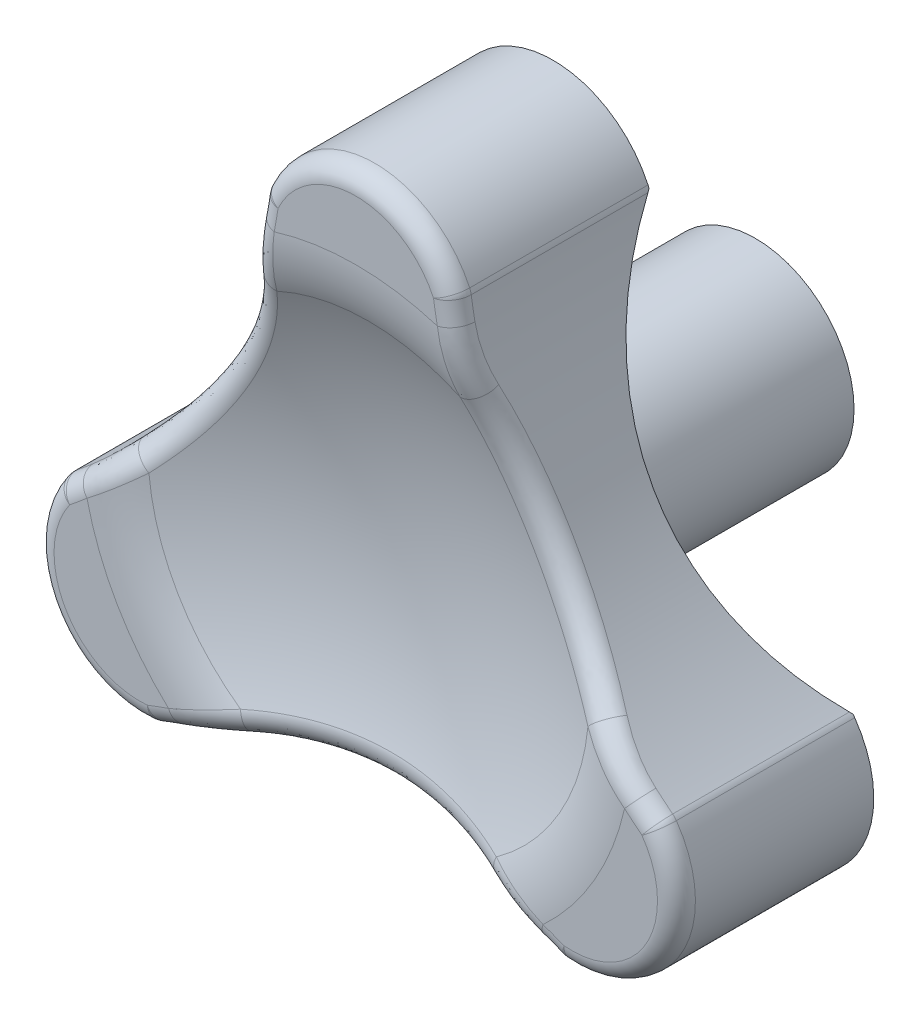
SolidWorks part; units mm, degrees
ref_plane "Front Plane" through (0, 0, 0) normal (0, 0, 1) x (1, 0, 0)
ref_plane "Top Plane" through (0, 0, 0) normal (0, 1, 0) x (1, 0, 0)
ref_plane "Right Plane" through (0, 0, 0) normal (1, 0, 0) x (0, 0, -1)
sketch "Sketch2" plane through (0, 0, 0) normal (0, 0, 1) x (1, 0, 0)
  circle A0 centre (0, 0) radius 7.8
  circle A1 centre (0, 0) radius 3
  dimension "D1" = 15.6
  dimension "D2" = 6
extrude "Boss-Extrude1" add sketch "Sketch2" against normal blind 16
sketch "Sketch3" plane through (0, 0, 0) normal (0, 0, 1) x (1, 0, 0)
  line L0 (0, 0) -> (0, 28) construction
  line L1 (7.6, 23) -> (-7.6, 23) construction
  line L2 (-24.2487, -14) -> (0, 0) construction
  line L3 (0, 0) -> (24.2487, -14) construction
  line L4 (12.9904, 7.5) -> (0, 0) construction
  line L5 (0, -15) -> (0, 0) construction
  line L6 (-12.9904, 7.5) -> (0, 0) construction
  arc A0 (-7.6, 23) -> (7.6, 23) centre (0, 19.724) cw
  circle A1 centre (0, 0) radius 3 construction
  circle A2 centre (0, 0) radius 3 construction
  arc A3 (23.7186, -4.9182) -> (16.1186, -18.0818) centre (17.0815, -9.862) cw
  arc A4 (-16.1186, -18.0818) -> (-23.7186, -4.9182) centre (-17.0815, -9.862) cw
  arc A5 (7.6, 23) -> (23.7186, -4.9182) centre (50.8297, 29.3466) ccw
  arc A6 (16.1186, -18.0818) -> (-16.1186, -18.0818) centre (0, -58.6931) ccw
  arc A7 (-23.7186, -4.9182) -> (-7.6, 23) centre (-50.8297, 29.3466) ccw
  point P6 (0, 23)
  point P7 (0, 28)
  point P20 (0, 0)
  point P33 (0, 0)
  dimension "D1" = 28
  dimension "D2" = 15.2
  dimension "D3" = 5
  dimension "D5" = 15
  dimension "D4" = 3
  dimension "D6" = 3
extrude "Boss-Extrude2" add sketch "Sketch3" along normal blind 15.6
sketch "Sketch4" plane through (0, 0, 0) normal (0, 1, 0) x (1, 0, 0)
  line L0 (16.1186, 0) -> (-16.1186, 0) construction
  line L1 (16.1186, 0) -> (-16.1186, 0)
  line L2 (0, 0) -> (0, -5) construction
  arc A0 (-16.1186, 0) -> (16.1186, 0) centre (0, 23.4809) ccw
  dimension "D1" = 5
extrude "Cut-Extrude1" cut sketch "Sketch4" against normal blind 15.6 from offset 7.8 offset against normal yes
pattern_circular "CirPattern1" count 3 over 360 about axis through (0, 0, -16) along (0, 0, 1) of "Cut-Extrude1"
sketch "Sketch5" plane through (0, 0, 0) normal (0, 0, -1) x (-1, 0, 0)
  line L0 (-13.51, -7.8) -> (13.51, -7.8) construction
  line L1 (13.51, -7.8) -> (0, 15.6) construction
  line L2 (0, 15.6) -> (-13.51, -7.8) construction
  line L3 (-13.51, -7.8) -> (13.51, -7.8)
  line L4 (13.51, -7.8) -> (0, 15.6)
  line L5 (0, 15.6) -> (-13.51, -7.8)
  circle A0 centre (0, 0) radius 7.8 construction
  arc A1 (-6.755, 3.9) -> (0, -7.8) centre (0, 0) ccw construction
  arc A2 (0, -7.8) -> (6.755, 3.9) centre (0, 0) ccw construction
  circle A3 centre (0, 0) radius 7.8
  arc A4 (-6.755, 3.9) -> (0, -7.8) centre (0, 0) ccw
  arc A5 (0, -7.8) -> (6.755, 3.9) centre (0, 0) ccw
  arc M1 (0, -7.8) -> (-6.755, 3.9) centre (0, 0) cw
  line M2 (-6.755, 3.9) -> (-13.51, -7.8)
  line M3 (-13.51, -7.8) -> (0, -7.8)
extrude "Cut-Extrude2" cut sketch "Sketch5" against normal blind 2 contours M3 M1 M2 | A3 L4 L5 | A3 L3 L4 region at (8.542, -4.9317, 0) region at (-8.542, -4.9317, 0) region at (0, 9.8634, 0)
sketch "Sketch7" plane through (0, 0, 0) normal (1, 0, 0) x (0, 0, -1)
  line L0 (0, 0) -> (-90.6, 0) construction
  line L1 (-15.6, 23) -> (-15.6, -4.9182) construction
  line L2 (-15.6, 23) -> (-15.6, -4.9182) construction
  line L3 (-10.6, 0) -> (-90.6, 0)
  arc A0 (-10.6, 0) -> (-90.6, 0) centre (-50.6, 0) ccw
  dimension "D2" = 40
  dimension "D1" = 10
  dimension "D3" = 50.6
revolve "Cut-Revolve1" cut sketch "Sketch7" angle 360 about L3
fillet "Fillet1" radius 10 3 edges at (16.7705, -9.6825, 15.6) (-16.7705, -9.6825, 15.6) (0, 19.3649, 15.6)
fillet "Fillet2" radius 1.5 18 edges at (-22.6308, -4.0287, 15.6) (-18.0509, 0.4565, 14.8752) (-7.8264, 21.6132, 15.6) (7.8264, 21.6132, 15.6) (9.4208, 15.4043, 14.8752) (22.6308, -4.0287, 15.6) (14.8044, -17.5845, 15.6) (8.6301, -15.8608, 14.8752) (-14.8044, -17.5845, 15.6) (-24.2487, -14, 15.6) (-14.4265, 5.1826, 13.6539) (0, 28, 15.6) (24.2487, -14, 15.6) (11.7016, 9.9024, 13.6539) (2.725, -15.0851, 13.6539)
fillet "Fillet3" radius 1.5 12 edges at (-7.2859, 22.9104, 15.0309) (-23.4839, -5.1454, 15.0309) (-16.198, -17.765, 15.0309) (16.198, -17.765, 15.0309) (23.4839, -5.1454, 15.0309) (7.2859, 22.9104, 15.0309) (-7.6, 23, 7.05) (-23.7186, -4.9182, 7.05) (-16.1186, -18.0818, 7.05) (16.1186, -18.0818, 7.05) (23.7186, -4.9182, 7.05) (7.6, 23, 7.05)
